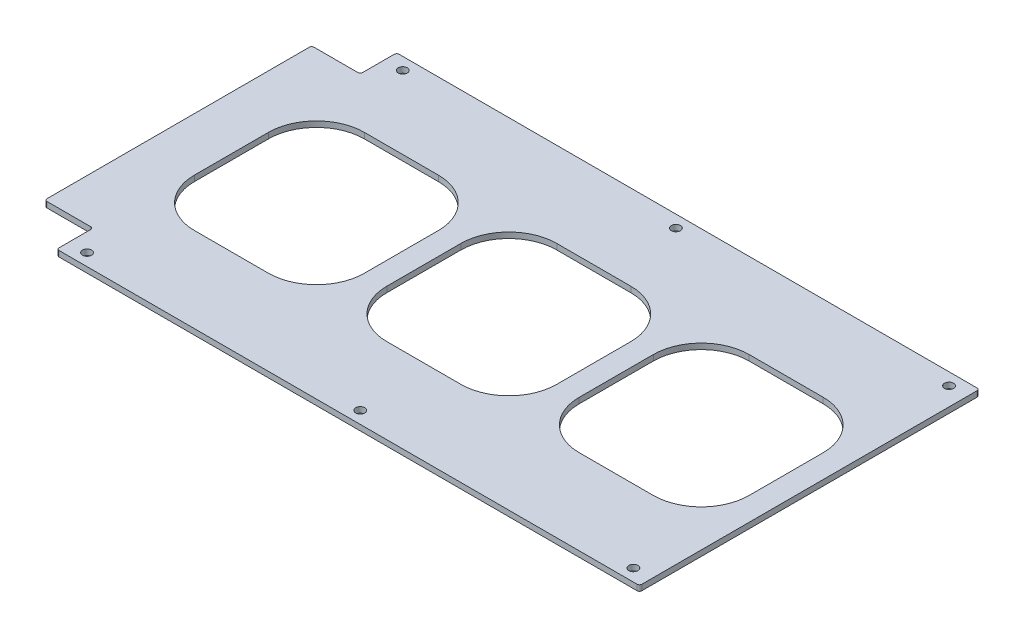
SolidWorks part; units mm, degrees
material "Acrylic (Medium-high impact)"
ref_plane "Front" through (0, 0, 0) normal (0, 0, 1) x (1, 0, 0)
ref_plane "Top" through (0, 0, 0) normal (0, 1, 0) x (1, 0, 0)
ref_plane "Right" through (0, 0, 0) normal (1, 0, 0) x (0, 0, -1)
sketch "Sketch1" plane through (0, 0, 0) normal (0, 1, 0) x (1, 0, 0)
  line L5 (-151.765, 88.9) -> (153.035, -88.9) construction
  line L6 (-151.765, -88.9) -> (151.765, 88.9) construction
  line L12 (-177.165, 69.85) -> (-151.765, -69.85) construction
  line L13 (-177.165, -69.85) -> (-151.765, 69.85) construction
  line L14 (-124.2065, 44.45) -> (-85.4715, 44.45)
  line L15 (-150.495, 88.9) -> (151.765, 88.9)
  line L20 (-149.289, 19.3675) -> (-149.289, -19.3675)
  line L21 (-124.2065, -44.45) -> (-85.4715, -44.45)
  line L26 (-60.389, 19.3675) -> (-60.389, -19.3675)
  line L27 (-149.289, 44.45) -> (-60.389, -44.45) construction
  line L32 (-149.289, -44.45) -> (-60.389, 44.45) construction
  line L33 (-23.5715, 44.45) -> (15.1635, 44.45)
  line L34 (153.035, 87.63) -> (153.035, -87.63)
  line L35 (151.765, -88.9) -> (-150.495, -88.9)
  line L36 (-151.765, -87.63) -> (-151.765, -71.12)
  line L37 (-153.035, -69.85) -> (-175.895, -69.85)
  line L38 (-177.165, -68.58) -> (-177.165, 68.58)
  line L39 (-175.895, 69.85) -> (-153.035, 69.85)
  line L40 (-151.765, 71.12) -> (-151.765, 87.63)
  line L41 (-48.654, 19.3675) -> (-48.654, -19.3675)
  line L42 (-23.5715, -44.45) -> (15.1635, -44.45)
  line L43 (40.246, 19.3675) -> (40.246, -19.3675)
  line L44 (-48.654, 44.45) -> (40.246, -44.45) construction
  line L45 (-48.654, -44.45) -> (40.246, 44.45) construction
  line L46 (77.0635, 44.45) -> (115.7985, 44.45)
  line L47 (51.981, 19.3675) -> (51.981, -19.3675)
  line L48 (77.0635, -44.45) -> (115.7985, -44.45)
  line L49 (140.881, 19.3675) -> (140.881, -19.3675)
  line L50 (51.981, 44.45) -> (140.881, -44.45) construction
  line L51 (51.981, -44.45) -> (140.881, 44.45) construction
  line L52 (-142.24, 82.55) -> (143.51, 82.55) construction
  line L53 (-142.24, 82.55) -> (-142.24, -82.55) construction
  line L54 (-142.24, -82.55) -> (143.51, -82.55) construction
  line L55 (143.51, 82.55) -> (143.51, -82.55) construction
  arc A0 (51.981, -19.3675) -> (77.0635, -44.45) centre (77.0635, -19.3675) ccw
  arc A1 (115.7985, -44.45) -> (140.881, -19.3675) centre (115.7985, -19.3675) ccw
  arc A2 (115.7985, 44.45) -> (140.881, 19.3675) centre (115.7985, 19.3675) cw
  arc A15 (-175.895, -69.85) -> (-177.165, -68.58) centre (-175.895, -68.58) cw
  arc A16 (-151.765, -71.12) -> (-153.035, -69.85) centre (-153.035, -71.12) ccw
  arc A17 (-150.495, -88.9) -> (-151.765, -87.63) centre (-150.495, -87.63) cw
  arc A18 (153.035, -87.63) -> (151.765, -88.9) centre (151.765, -87.63) cw
  arc A19 (151.765, 88.9) -> (153.035, 87.63) centre (151.765, 87.63) cw
  arc A20 (-150.495, 88.9) -> (-151.765, 87.63) centre (-150.495, 87.63) ccw
  arc A21 (-177.165, 68.58) -> (-175.895, 69.85) centre (-175.895, 68.58) cw
  arc A22 (77.0635, 44.45) -> (51.981, 19.3675) centre (77.0635, 19.3675) ccw
  arc A23 (-48.654, -19.3675) -> (-23.5715, -44.45) centre (-23.5715, -19.3675) ccw
  arc A24 (15.1635, -44.45) -> (40.246, -19.3675) centre (15.1635, -19.3675) ccw
  arc A25 (15.1635, 44.45) -> (40.246, 19.3675) centre (15.1635, 19.3675) cw
  arc A26 (-23.5715, 44.45) -> (-48.654, 19.3675) centre (-23.5715, 19.3675) ccw
  arc A27 (-149.289, -19.3675) -> (-124.2065, -44.45) centre (-124.2065, -19.3675) ccw
  arc A28 (-85.4715, -44.45) -> (-60.389, -19.3675) centre (-85.4715, -19.3675) ccw
  arc A29 (-85.4715, 44.45) -> (-60.389, 19.3675) centre (-85.4715, 19.3675) cw
  arc A30 (-124.2065, 44.45) -> (-149.289, 19.3675) centre (-124.2065, 19.3675) ccw
  circle A31 centre (-142.24, 82.55) radius 2.3813
  arc A32 (-155.093, -24.1463) -> (-54.585, -24.1463) centre (-104.839, 0) ccw construction
  arc A33 (-54.458, -24.1463) -> (46.05, -24.1463) centre (-4.204, 0) ccw construction
  arc A34 (46.177, -24.1463) -> (146.685, -24.1463) centre (96.431, 0) ccw construction
  arc A35 (-153.035, 69.85) -> (-151.765, 71.12) centre (-153.035, 71.12) ccw
  circle A36 centre (143.51, 82.55) radius 2.3813
  circle A37 centre (0.635, 82.55) radius 2.3813
  circle A38 centre (-142.24, -82.55) radius 2.3813
  circle A39 centre (0.635, -82.55) radius 2.3813
  circle A40 centre (143.51, -82.55) radius 2.3813
  point P0 (-104.839, 0)
  point P4 (0, 0)
  point P13 (-4.204, 0)
  point P18 (96.431, 0)
  dimension "D6" = 25.0825
  dimension "D7" = 1.27
  dimension "D8" = 1.27
  dimension "D13" = 4.7625
  dimension "D1" = 177.8
  dimension "D2" = 304.8
  dimension "D3" = 139.7
  dimension "D4" = 25.4
  dimension "D5" = 88.9
  dimension "D9" = 285.75
  dimension "D10" = 165.1
  dimension "D11" = 9.525
  dimension "D12" = 6.35
extrude "Boss-Extrude1" add sketch "Sketch1" along normal blind 2.9718
